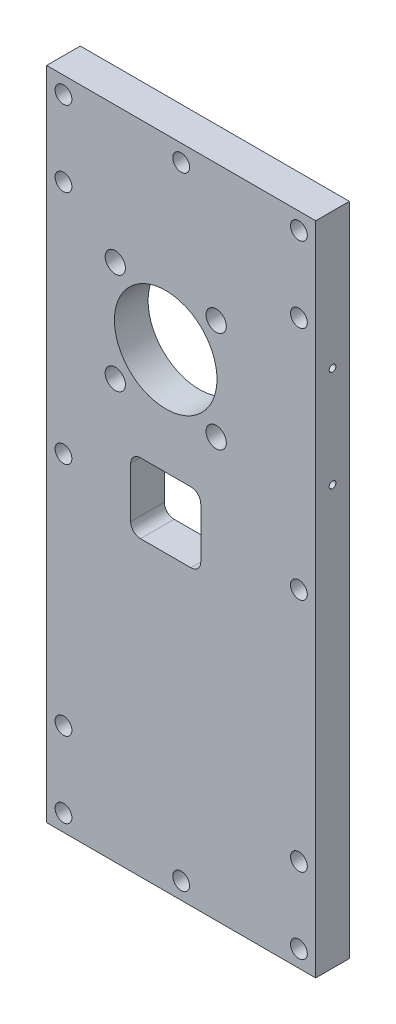
SolidWorks part; units mm, degrees
ref_plane "Ebene vorne" through (0, 0, 0) normal (0, 0, 1) x (1, 0, 0)
ref_plane "Ebene oben" through (0, 0, 0) normal (0, 1, 0) x (1, 0, 0)
ref_plane "Ebene rechts" through (0, 0, 0) normal (1, 0, 0) x (0, 0, -1)
sketch "Skizze1" plane through (0, 0, 0) normal (0, 0, 1) x (1, 0, 0)
  line L1 (-69.0594, 70.0995) -> (10.9406, 70.0995)
  line L2 (-69.0594, 70.0995) -> (-69.0594, -124.9005)
  line L3 (-69.0594, -124.9005) -> (10.9406, -124.9005)
  line L4 (10.9406, 70.0995) -> (10.9406, -124.9005)
  dimension "D1" = 195
  dimension "D2" = 80
extrude "Aufsatz-Linear austragen1" add sketch "Skizze1" against normal blind 10
sketch "Skizze2" plane through (0, 0, -10) normal (0, 0, -1) x (-1, 0, 0)
  line L0 (69.0594, 70.0995) -> (69.0594, -124.9005) construction
  line L1 (33.6594, 14.5995) -> (33.6594, -27.4005) construction
  line L3 (33.6594, 14.5995) -> (69.0594, 14.5995) construction
  line L5 (18.6594, 29.5995) -> (48.6594, 29.5995) construction
  line L6 (48.6594, 29.5995) -> (48.6594, -0.4005) construction
  line L7 (48.6594, -0.4005) -> (18.6594, -0.4005) construction
  line L8 (18.6594, -0.4005) -> (18.6594, 29.5995) construction
  line L9 (18.6594, 29.5995) -> (48.6594, -0.4005) construction
  line L10 (69.0594, -27.4005) -> (-10.9406, -27.4005) construction
  line L11 (-10.9406, -124.9005) -> (-10.9406, 70.0995) construction
  line L12 (23.2413, -19.9005) -> (23.2413, -34.9005)
  line L13 (26.1594, -16.9824) -> (41.1594, -16.9824)
  line L14 (44.0774, -19.9005) -> (44.0774, -34.9005)
  line L15 (41.1594, -37.8185) -> (26.1594, -37.8185)
  line L16 (23.2413, -19.9005) -> (44.0774, -34.9005) construction
  line L17 (26.1594, -37.8185) -> (41.1594, -16.9824) construction
  circle A0 centre (18.6594, 29.5995) radius 3.015
  circle A1 centre (48.6594, 29.5995) radius 3.015
  circle A2 centre (18.6594, -0.4005) radius 3.015
  circle A3 centre (48.6594, -0.4005) radius 3.015
  circle A4 centre (33.6594, 14.5995) radius 15.25
  arc A5 (23.2413, -19.9005) -> (26.1594, -16.9824) centre (26.1594, -19.9005) cw
  arc A6 (41.1594, -16.9824) -> (44.0774, -19.9005) centre (41.1594, -19.9005) cw
  arc A7 (44.0774, -34.9005) -> (41.1594, -37.8185) centre (41.1594, -34.9005) cw
  arc A8 (26.1594, -37.8185) -> (23.2413, -34.9005) centre (26.1594, -34.9005) cw
  point P22 (33.6594, 14.5995)
  point P32 (33.6594, -27.4005)
  dimension "D1" = 30
  dimension "D3" = 6.03
  dimension "D2" = 30
  dimension "D4" = 35.4
  dimension "D5" = 42
  dimension "D6" = 15
extrude "Schnitt-Linear austragen1" cut sketch "Skizze2" against normal blind 10
sketch "Skizze3" plane through (0, 0, -10) normal (0, 0, -1) x (-1, 0, 0)
  line L0 (-5.9406, 65.0995) -> (63.8159, 65.0995) construction
  line L1 (63.8159, 65.0995) -> (63.8159, 42.5995) construction
  line L2 (63.8159, 42.5995) -> (63.8159, -27.4005) construction
  line L4 (63.8159, -27.4005) -> (63.8159, -97.4005) construction
  line L5 (63.8159, -97.4005) -> (63.8159, -119.9005) construction
  line L6 (63.8159, -119.9005) -> (-5.9406, -119.9005) construction
  line L7 (-5.9406, -119.9005) -> (-5.9406, -97.4005) construction
  line L8 (-5.9406, -97.4005) -> (-5.9406, -27.4005) construction
  line L10 (-5.9406, -27.4005) -> (-5.9406, 42.5995) construction
  line L11 (-5.9406, 42.5995) -> (-5.9406, 65.0995) construction
  line L12 (28.9377, 65.0995) -> (29.0594, 70.0995) construction
  line L13 (-10.9406, 70.0995) -> (69.0594, 70.0995) construction
  line L14 (28.9377, -119.9005) -> (29.0594, -124.9005) construction
  line L15 (69.0594, -124.9005) -> (-10.9406, -124.9005) construction
  line L16 (-10.9406, -124.9005) -> (-10.9406, 70.0995) construction
  circle A0 centre (-5.9406, 65.0995) radius 1.25
  circle A1 centre (63.8159, 65.0995) radius 1.25
  circle A2 centre (28.9377, 65.0995) radius 1.25
  circle A3 centre (63.8159, 42.5995) radius 1.25
  circle A5 centre (63.8159, -27.4005) radius 1.25
  circle A6 centre (63.8159, -97.4005) radius 1.25
  circle A7 centre (63.8159, -119.9005) radius 1.25
  circle A8 centre (28.9377, -119.9005) radius 1.25
  circle A9 centre (-5.9406, -119.9005) radius 1.25
  circle A10 centre (-5.9406, -97.4005) radius 1.25
  circle A11 centre (-5.9406, -27.4005) radius 1.25
  circle A13 centre (-5.9406, 42.5995) radius 1.25
  dimension "D4" = 2.5
  dimension "D1" = 5
  dimension "D2" = 5
  dimension "D3" = 5
  dimension "D5" = 70
extrude "Schnitt-Linear austragen2" cut sketch "Skizze3" against normal blind 5
sketch "Skizze4" plane through (0, 0, 0) normal (0, 0, 1) x (1, 0, 0)
  line L0 (-64.0594, 65.0995) -> (-64.0594, 42.5995) construction
  line L1 (-64.0594, 42.5995) -> (-64.0594, -27.4005) construction
  line L2 (-64.0594, -27.4005) -> (-64.0594, -97.4005) construction
  line L3 (-64.0594, -97.4005) -> (-64.0594, -119.9005) construction
  line L4 (5.9406, 65.0995) -> (5.9406, 42.5995) construction
  line L5 (5.9406, -119.9005) -> (-64.0594, -119.9005) construction
  line L6 (5.9406, 42.5995) -> (5.9406, -27.4005) construction
  line L7 (5.9406, -27.4005) -> (5.9406, -97.4005) construction
  line L8 (5.9406, -97.4005) -> (5.9406, -119.9005) construction
  line L11 (-64.0594, 65.0995) -> (5.9406, 65.0995) construction
  line L12 (-29.0594, 65.0995) -> (-29.0594, 70.0995) construction
  line L13 (10.9406, 70.0995) -> (-69.0594, 70.0995) construction
  line L15 (-69.0594, -124.9005) -> (10.9406, -124.9005) construction
  circle A0 centre (-64.0594, 65.0995) radius 2.5
  circle A1 centre (5.9406, 65.0995) radius 2.5
  circle A2 centre (5.9406, 42.5995) radius 2.5
  circle A3 centre (5.9406, -27.4005) radius 2.5
  circle A5 centre (5.9406, -97.4005) radius 2.5
  circle A6 centre (5.9406, -119.9005) radius 2.5
  circle A7 centre (-64.0594, -119.9005) radius 2.5
  circle A8 centre (-64.0594, -97.4005) radius 2.5
  circle A10 centre (-64.0594, -27.4005) radius 2.5
  circle A11 centre (-64.0594, 42.5995) radius 2.5
  circle A12 centre (-29.0594, -119.9005) radius 2.5
  circle A13 centre (-29.0594, 65.0995) radius 2.5
  dimension "D4" = 5
  dimension "D1" = 70
  dimension "D2" = 5
  dimension "D3" = 5
extrude "Schnitt-Linear austragen3" cut sketch "Skizze4" against normal blind 5
sketch "Skizze5" plane through (-69.0594, 0, 0) normal (-1, 0, 0) x (0, 0, 1)
  line L0 (0, 14.5995) -> (-10, 14.5995) construction
  line L1 (-5, 14.5995) -> (-5, -0.4005) construction
  line L2 (-5, 14.5995) -> (-5, 29.5995) construction
  line L3 (-10, 70.0995) -> (-10, -124.9005) construction
  line L4 (0, 70.0995) -> (0, -124.9005) construction
  line L5 (-10, 70.0995) -> (0, 70.0995) construction
  circle A0 centre (-5, 29.5995) radius 1
  circle A1 centre (-5, -0.4005) radius 1
  point P7 (-10, 18.4372)
  point P10 (0, 18.3413)
  dimension "D1" = 2
  dimension "D2" = 30
  dimension "D3" = 55.5
extrude "Schnitt-Linear austragen4" cut sketch "Skizze5" against normal blind 20
sketch "Skizze6" plane through (10.9406, 0, 0) normal (1, 0, 0) x (0, 0, -1)
  line L0 (10, 14.5995) -> (0, 14.5995) construction
  line L1 (5, 14.5995) -> (5, -0.4005) construction
  line L2 (5, 14.5995) -> (5, 29.5995) construction
  line L3 (0, -124.9005) -> (0, 70.0995) construction
  line L4 (10, -124.9005) -> (10, 70.0995) construction
  line L5 (10, 70.0995) -> (0, 70.0995) construction
  circle A0 centre (5, 29.5995) radius 1
  circle A1 centre (5, -0.4005) radius 1
  point P7 (0, 34.832)
  point P10 (10, 35.4787)
  dimension "D1" = 2
  dimension "D2" = 30
  dimension "D3" = 55.5
extrude "Schnitt-Linear austragen5" cut sketch "Skizze6" against normal blind 30
